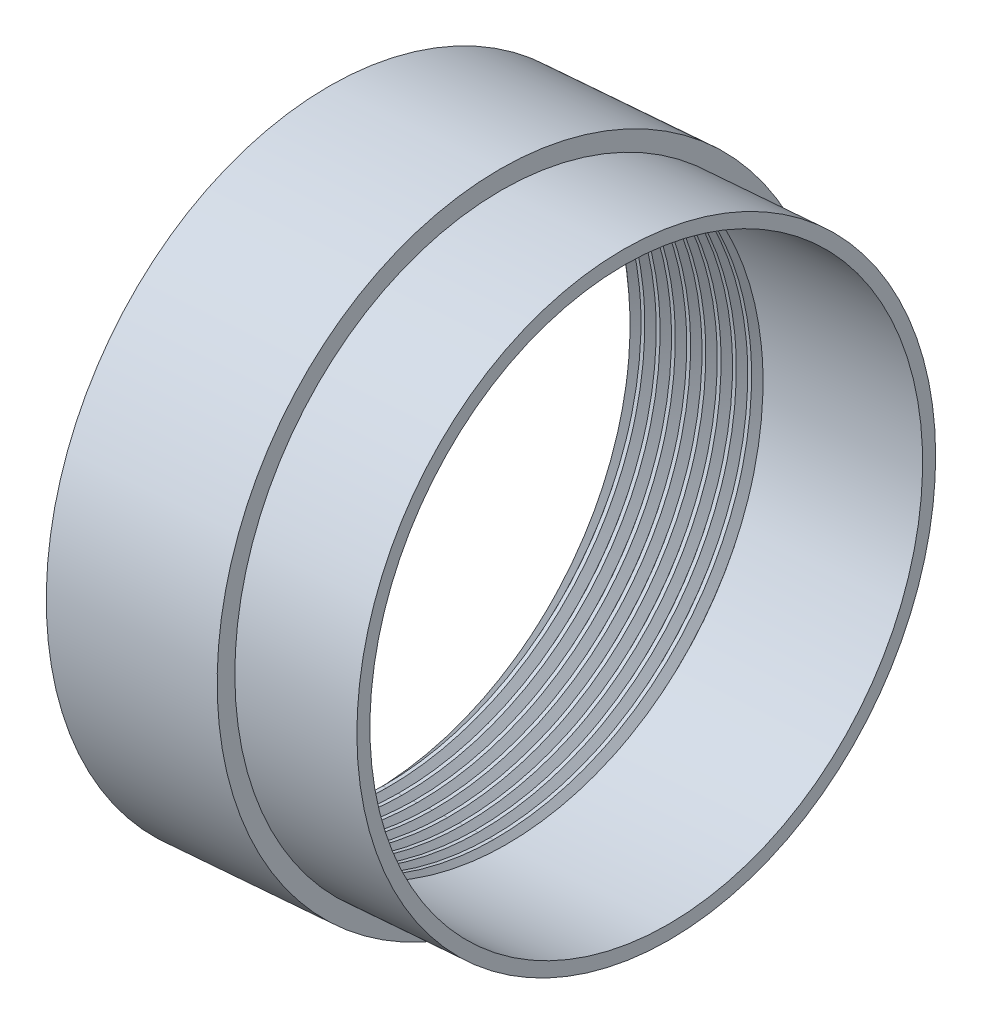
SolidWorks part; units mm, degrees
ref_plane "Front Plane" through (0, 0, 0) normal (0, 0, 1) x (1, 0, 0)
ref_plane "Top Plane" through (0, 0, 0) normal (0, 1, 0) x (1, 0, 0)
ref_plane "Right Plane" through (0, 0, 0) normal (1, 0, 0) x (0, 0, -1)
sketch "Sketch3" plane through (-310.5359, -24.7684, 0) normal (-0.9968, -0.0795, 0) x (0, 0, 1)
  circle A4 centre (43.1743, 14.6524) radius 14.9605
  circle A6 centre (43.1743, 14.6524) radius 14.2875
  dimension "D1" = 29.921
  dimension "D2" = 28.575
extrude "Boss-Extrude3" add sketch "Sketch3" against normal blind 6.35
sketch "Sketch4" plane through (-310.5359, -24.7684, 0) normal (-0.9968, -0.0795, 0) x (0, 0, 1)
  circle A1 centre (43.1743, 14.6524) radius 15.875
  circle A3 centre (43.1743, 14.6524) radius 14.2875
  dimension "D1" = 31.75
  dimension "D2" = 28.575
extrude "Boss-Extrude4" add sketch "Sketch4" along normal blind 8.89
thread "Thread1" pitch 0.7937 method cut profile "Thread Profile1" start angle 0, offset 0.7937, length 7.62, pitch 0.7937, diameter 28.575
ref_plane "Plane1" through (-321.3539, -10.9323, 28.8868) normal (0.0795, -0.9968, 0) x (0, 0, -1)
sketch "Thread Profile1" plane through (-321.3539, -10.9323, 28.8868) normal (0.0795, -0.9968, 0) x (0, 0, -1)
  line L0 (0, 0) -> (0, 0.7937) construction
  line L1 (0, 0) -> (0.4296, 0.248)
  line L2 (0.4296, 0.248) -> (0.4296, 0.3473)
  line L3 (0.4296, 0.3473) -> (0, 0.5953)
  line L4 (0.4296, 0.2977) -> (0, 0.2977) construction
  line L11 (0, 0) -> (0, 0.5953)
  point P2 (0, 0)
  dimension "Pitch" = 0.7937
  dimension "Profile_Angle" = 60
  dimension "Profile_Land" = 0.0992
  dimension "Profile_Height" = 0.4296
sketch "Sketch8" plane through (-319.3977, -25.4752, 0) normal (-0.9968, -0.0795, 0) x (0, 0, 1)
  arc A0 (48.8063, 1.0555) -> (56.7711, 9.0204) centre (43.1743, 14.6524) ccw construction
  arc A1 (48.8063, 1.0555) -> (56.7711, 9.0204) centre (43.1743, 14.6524) ccw
  dimension "D1" = 14.7171
